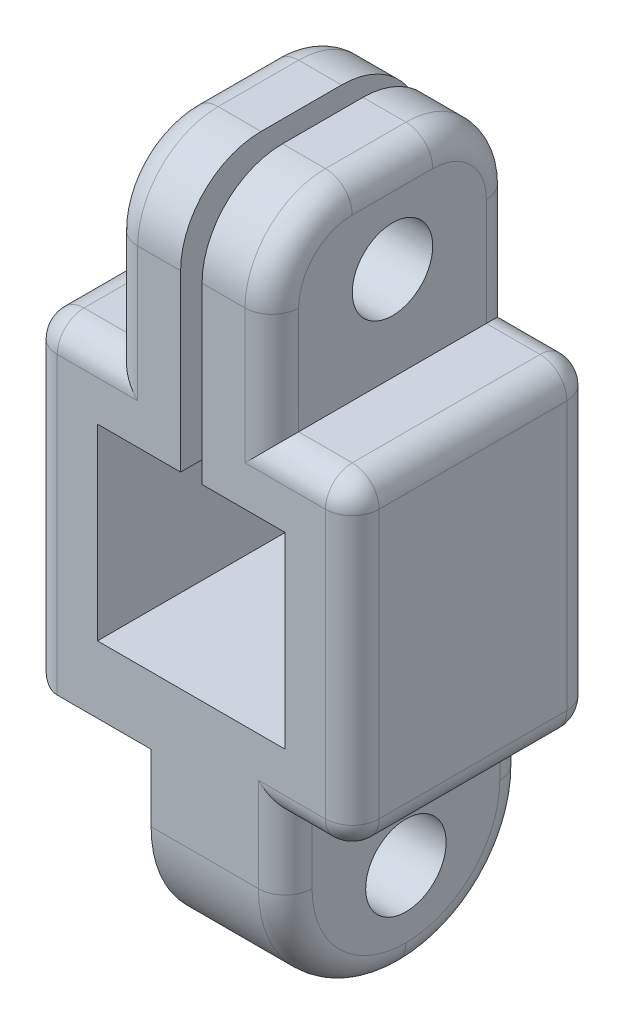
SolidWorks part; units mm, degrees
ref_plane "前视基准面" through (0, 0, 0) normal (0, 0, 1) x (1, 0, 0)
ref_plane "上视基准面" through (0, 0, 0) normal (0, 1, 0) x (1, 0, 0)
ref_plane "右视基准面" through (0, 0, 0) normal (1, 0, 0) x (0, 0, -1)
sketch "草图1" plane through (0, 0, 0) normal (0, 0, 1) x (1, 0, 0)
  line L0 (-1.5, -6) -> (-1.5, -13)
  line L1 (-3.5, 3.5) -> (3.5, 3.5)
  line L2 (-3.5, 3.5) -> (-3.5, -3.5)
  line L3 (-3.5, -3.5) -> (3.5, -3.5)
  line L4 (3.5, 3.5) -> (3.5, -3.5)
  line L5 (-3.5, 3.5) -> (3.5, -3.5) construction
  line L6 (-3.5, -3.5) -> (3.5, 3.5) construction
  line L7 (-6, 6) -> (6, 6)
  line L8 (-6, 6) -> (-6, -6)
  line L9 (-6, -6) -> (6, -6)
  line L10 (6, 6) -> (6, -6)
  line L11 (-6, 6) -> (6, -6) construction
  line L12 (-6, -6) -> (6, 6) construction
  line L13 (-1.5, -13) -> (3.5, -13)
  line L14 (3.5, -13) -> (3.5, -6)
  line L15 (0, 0) -> (0, 9.9638) construction
  line L17 (0, 6) -> (3, 6)
  line L18 (0, 6) -> (0, 13)
  line L19 (0, 13) -> (3, 13)
  line L20 (3, 6) -> (3, 13)
  line L21 (0, 6) -> (-3, 6)
  line L22 (0, 6) -> (0, 13)
  line L23 (0, 13) -> (-3, 13)
  line L24 (-3, 6) -> (-3, 13)
  point P0 (0, 0)
  point P6 (0, 0)
  dimension "D1" = 7
  dimension "D2" = 7
  dimension "D3" = 12
  dimension "D4" = 12
  dimension "D5" = 2
  dimension "D6" = 7
  dimension "D7" = 5
  dimension "D8" = 7
  dimension "D9" = 3
  dimension "D10" = 3
  dimension "D11" = 7
extrude "凸台-拉伸1" add sketch "草图1" along normal blind 9 contours L24 L7 L18 L23 | L7 L20 L19 L18 | L10 L7 L8 L9 L1 L4 L3 L2 | L13 L14 L9 L0 region at (1, -9.5, 0) region at (-3.75, -5.8303, 0) region at (-1.5, 9.5, 0) region at (1.5, 9.5, 0)
sketch "草图2" plane through (0, 0, 9) normal (0, 0, 1) x (1, 0, 0)
  line L0 (0, 16.6392) -> (0, -1.0512) construction
  line L1 (3, 13) -> (-3, 13) construction
  line L2 (0, 13) -> (0.4, 13)
  line L4 (0, 3.5) -> (0.4, 3.5)
  line L5 (0.4, 13) -> (0.4, 3.5)
  line L6 (-3.5, 3.5) -> (3.5, 3.5) construction
  line L8 (0, 13) -> (-0.4, 13)
  line L10 (0, 3.5) -> (-0.4, 3.5)
  line L11 (-0.4, 13) -> (-0.4, 3.5)
  dimension "D1" = 0.4
  dimension "D2" = 0.4
extrude "切除-拉伸1" cut sketch "草图2" against normal through all contours L2 L5 L4 L10 L11 L8
fillet "圆角1" radius 4.5 2 edges at (1, -13, 0) (1, -13, 9)
sketch "草图3" plane through (3.5, 0, 0) normal (1, 0, 0) x (0, 0, -1)
  line L0 (-4.5, -6) -> (-4.5, -9.5) construction
  line L2 (-9, -6) -> (0, -6) construction
  circle A0 centre (-4.5, -9.5) radius 1.5
  dimension "D2" = 3
  dimension "D1" = 3.5
extrude "切除-拉伸2" cut sketch "草图3" against normal through all
fillet "圆角2" radius 3 4 edges at (1.7, 13, 0) (-1.7, 13, 0) (-1.7, 13, 9) (1.7, 13, 9)
sketch "草图4" plane through (3, 0, 0) normal (1, 0, 0) x (0, 0, -1)
  line L0 (-4.5, 6) -> (-4.5, 9.5) construction
  line L1 (-9, 6) -> (0, 6) construction
  circle A0 centre (-4.5, 9.5) radius 1.5
  dimension "D2" = 3
  dimension "D1" = 3.5
extrude "切除-拉伸3" cut sketch "草图4" against normal through all
fillet "圆角3" radius 1 11 edges at (3, 8, 0) (3, 12.1213, 0.8787) (3, 13, 4.5) (3, 12.1213, 8.1213) (3, 8, 9) (6, -6, 4.5) (6, 0, 0) (6, 0, 9) (6, 6, 4.5) (4.5, 6, 0) (4.5, 6, 9)
fillet "圆角4" radius 1 10 edges at (-3, 8, 0) (-3, 12.1213, 0.8787) (-3, 13, 4.5) (-3, 12.1213, 8.1213) (-3, 8, 9) (-6, -6, 4.5) (-6, 0, 0) (-4.5, 6, 0) (-4.5, 6, 9) (-6, 0, 9)
fillet "圆角5" radius 1 3 edges at (-5.7071, 5.7071, 8.7071) (-5.7071, 5.7071, 0.2929) (-6, 6, 4.5)
fillet "圆角6" radius 1 8 edges at (5.7071, -5.7071, 0.2929) (5.7071, -5.7071, 8.7071) (3.5, -7.25, 9) (3.5, -7.25, 0) (3.5, -11.682, 1.318) (4.25, -6, 0) (4.25, -6, 9) (3.5, -11.682, 7.682)
